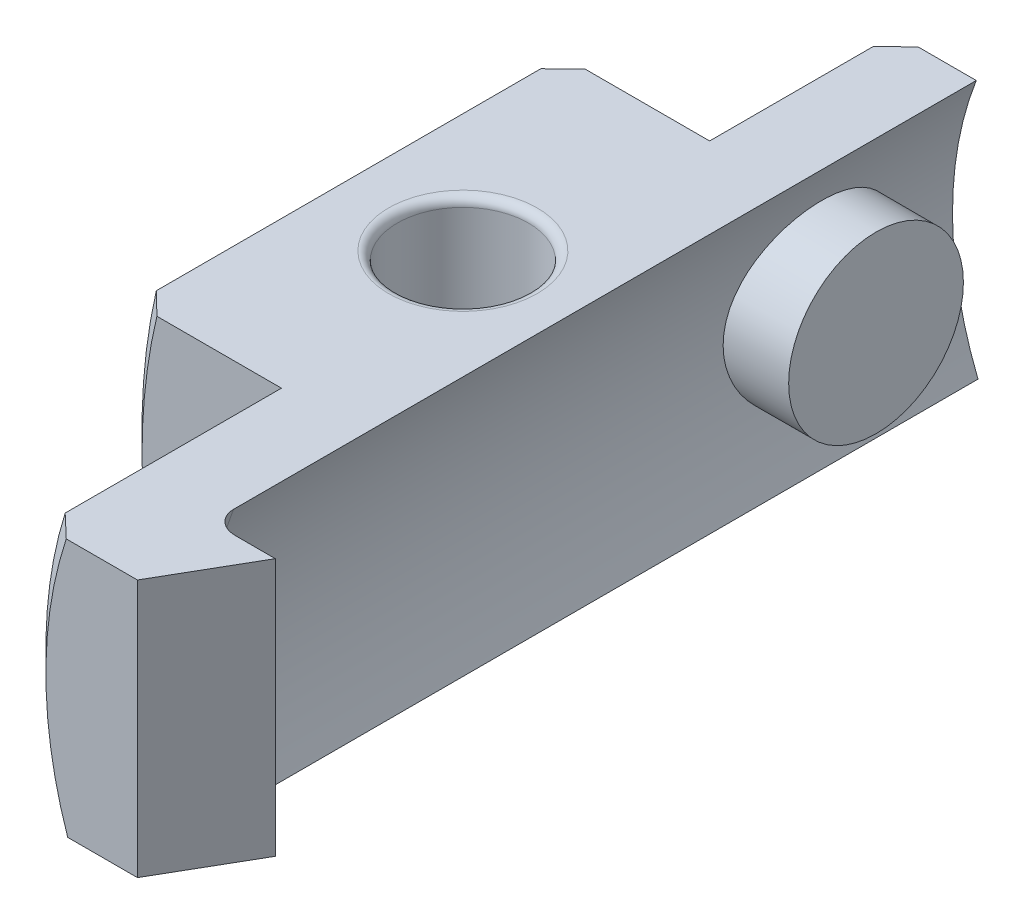
SolidWorks part; units mm, degrees
ref_plane "정면" through (0, 0, 0) normal (0, 0, 1) x (1, 0, 0)
ref_plane "윗면" through (0, 0, 0) normal (0, 1, 0) x (1, 0, 0)
ref_plane "우측면" through (0, 0, 0) normal (1, 0, 0) x (0, 0, -1)
sketch "스케치2" plane through (0, 0, 0) normal (0, 0, 1) x (1, 0, 0)
  line L1 (-7.4559, 2.9) -> (-9.3087, 2.9)
  line L2 (-7.4162, -3) -> (-9.277, -3)
  arc A0 (-7.4559, 2.9) -> (-7.4162, -3) centre (0, 0) ccw
  arc A1 (-9.3087, 2.9) -> (-9.277, -3) centre (0, 0) ccw
  point P5 (-8, 0)
  dimension "D1" = 16
  dimension "D3" = 19.5
  dimension "D2" = 5.9
extrude "보스-돌출2" add sketch "스케치2" along normal blind 19.5 contours A1 L2 A0 L1
ref_plane "평면1" through (-8, 0, 0) normal (1, 0, 0) x (0, 0, -1)
sketch "스케치3" plane through (-8, 0, 0) normal (1, 0, 0) x (0, 0, -1)
  line L0 (0, -3) -> (0, 2.9) construction
  circle A0 centre (-3.25, 0) radius 2
  point P2 (0, -0.05)
  dimension "D1" = 4
  dimension "D2" = 3.25
extrude "보스-돌출3" add sketch "스케치3" along normal blind 1.5
ref_plane "평면2" through (-9.75, 0, 0) normal (-1, 0, 0) x (0, 0, 1)
sketch "스케치4" plane through (-9.75, 0, 0) normal (-1, 0, 0) x (0, 0, 1)
  line L0 (0, 0) -> (4.25, 0) construction
  line L1 (4.25, 0) -> (14.05, 0) construction
  line L2 (4.25, 2.9) -> (4.25, -3)
  line L3 (19.5, 2.9) -> (0, 2.9) construction
  line L4 (19.5, -3) -> (0, -3) construction
  line L5 (4.25, -3) -> (14.05, -3)
  line L6 (14.05, -3) -> (14.05, 2.9)
  line L7 (14.05, 2.9) -> (4.25, 2.9)
  dimension "D1" = 4.25
  dimension "D2" = 9.8
extrude "보스-돌출4" add sketch "스케치4" along normal mid plane 1
extrude "보스-돌출5" add sketch "스케치4<3>" along normal blind 8
sketch "스케치4<3>" plane through (-9.75, 0, 0) normal (-1, 0, 0) x (0, 0, 1) same geometry as "스케치4"
sketch "스케치6" plane through (0, 0, 14.05) normal (0, 0, 1) x (1, 0, 0)
  line L0 (-12.6724, 2.9) -> (-17.75, 2.9)
  line L2 (-17.75, 2.9) -> (-9.3087, 2.9) construction
  line L3 (-17.75, 2.9) -> (-17.75, -3)
  line L4 (-17.75, -3) -> (-12.6491, -3)
  line L5 (-17.75, -3) -> (-9.277, -3) construction
  arc A0 (-12.6724, 2.9) -> (-12.6491, -3) centre (0, 0) ccw
  dimension "D1" = 13
extrude "컷-돌출1" cut sketch "스케치6" against normal through all
sketch "스케치7" plane through (0, 2.9, 0) normal (0, 1, 0) x (1, 0, 0)
  circle A0 centre (-9.9559, -9.25) radius 1.5
  point P11 (-12.0129, -10.25)
  dimension "D2" = 3
  dimension "D1" = 2.057
  dimension "D3" = 1
  dimension "D4" = 9.25
extrude "컷-돌출2" cut sketch "스케치7" against normal through all contours A0
fillet "필렛1" radius 0.2 2 edges at (-11.4559, -3, 9.25) (-11.4559, 2.9, 9.25)
sketch "스케치8" plane through (-8, 0, 0) normal (1, 0, 0) x (0, 0, -1)
  line L0 (-19.5, 2.9) -> (-19.5, -3)
  line L1 (-19.5, -3) -> (-17.5, -3)
  line L2 (-19.5, -3) -> (0, -3) construction
  line L3 (-17.5, -3) -> (-17.5, 2.9)
  line L4 (-19.5, 2.9) -> (0, 2.9) construction
  line L5 (-17.5, 2.9) -> (-19.5, 2.9)
  dimension "D1" = 2
extrude "보스-돌출6" add sketch "스케치8" along normal blind 2
chamfer "모따기1" distance 2 angle 30 1 edges at (-6, -0.05, 19.5) first distance on face at (-6, -0.05, 18.5)
fillet "필렛2" radius 0.5 1 edges at (-7.9998, -0.0538, 17.5)
chamfer "모따기2" distance 0.5 angle 45 4 edges at (-12.9999, -0.0513, 4.25) (-12.9999, -0.0513, 14.05) (-9.7499, -0.0525, 0) (-9.7499, -0.0525, 19.5)
